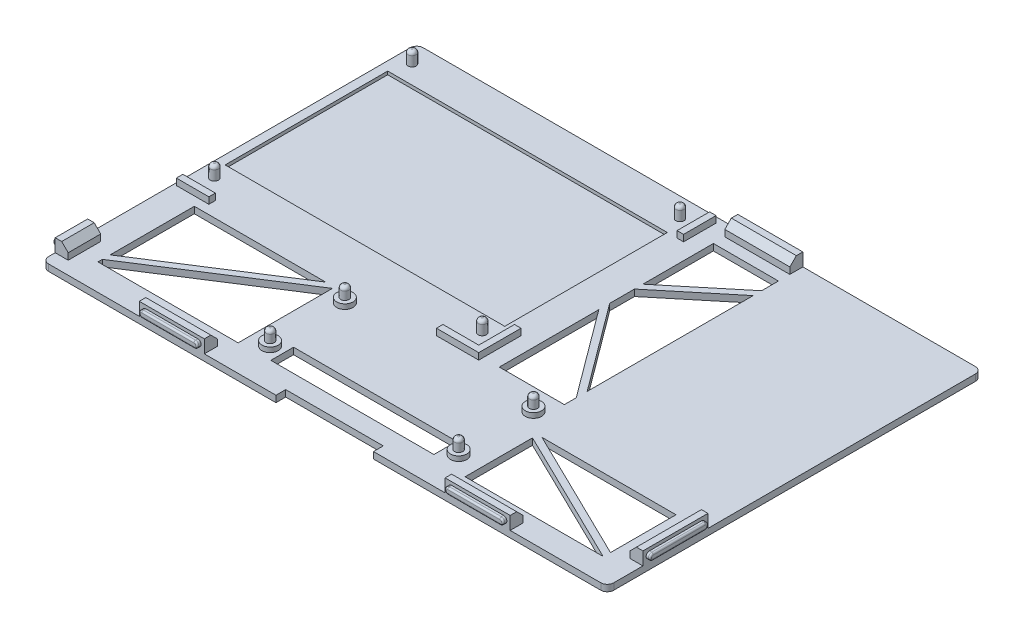
SolidWorks part; units mm, degrees
ref_plane "前基準面" through (0, 0, 0) normal (0, 0, 1) x (1, 0, 0)
ref_plane "上基準面" through (0, 0, 0) normal (0, 1, 0) x (1, 0, 0)
ref_plane "右基準面" through (0, 0, 0) normal (1, 0, 0) x (0, 0, -1)
sketch "草圖1" plane through (0, 0, 0) normal (0, 1, 0) x (1, 0, 0)
  line L0 (0, 57.6) -> (0, -57.6) construction
  line L1 (-86.9, 57.6) -> (86.9, 57.6)
  line L2 (-86.9, 57.6) -> (-86.9, -57.6)
  line L3 (-86.9, -57.6) -> (86.9, -57.6)
  line L4 (86.9, 57.6) -> (86.9, -57.6)
  line L5 (-86.9, 57.6) -> (86.9, -57.6) construction
  line L6 (-86.9, -57.6) -> (86.9, 57.6) construction
  line L7 (-86.9, 0) -> (86.9, 0) construction
  point P0 (0, 0)
  dimension "D1" = 173.8
  dimension "D2" = 115.2
extrude "填料-伸長1" add sketch "草圖1" along normal blind 2
sketch "草圖2" plane through (0, 2, 0) normal (0, 1, 0) x (1, 0, 0)
  line L0 (-86.9, 57.6) -> (-86.9, -57.6) construction
  line L1 (-86.16, 55.93) -> (3.84, 55.93)
  line L2 (-86.16, 55.93) -> (-86.16, -14.07)
  line L3 (-86.16, -14.07) -> (3.84, -14.07)
  line L4 (3.84, 55.93) -> (3.84, -14.07)
  line L5 (-86.16, 55.93) -> (3.84, -14.07) construction
  line L6 (-86.16, -14.07) -> (3.84, 55.93) construction
  line L7 (86.9, 57.6) -> (-86.9, 57.6) construction
  line L8 (-41.16, 55.93) -> (-41.16, -14.07) construction
  line L9 (-86.16, 20.93) -> (3.84, 20.93) construction
  point P0 (-41.16, 20.93)
  dimension "D1" = 90
  dimension "D2" = 70
  dimension "D3" = 0.74
  dimension "D4" = 1.67
sketch "草圖3" plane through (0, 2, 0) normal (0, 1, 0) x (1, 0, 0)
  line L0 (3.84, 55.93) -> (3.84, -14.07) construction
  line L1 (4.84, 55.93) -> (6.84, 55.93)
  line L2 (4.84, 55.93) -> (4.84, 45.93)
  line L3 (4.84, 45.93) -> (6.84, 45.93)
  line L4 (6.84, 55.93) -> (6.84, 45.93)
  line L5 (-86.16, -14.07) -> (3.84, -14.07) construction
  line L7 (4.84, -14.07) -> (4.84, -4.07)
  line L8 (4.84, -4.07) -> (6.84, -4.07)
  line L9 (6.84, -14.07) -> (6.84, -4.07)
  line L10 (6.84, -17.07) -> (-6.16, -17.07)
  line L11 (6.84, -17.07) -> (6.84, -15.07)
  line L12 (4.84, -15.07) -> (-6.16, -15.07)
  line L13 (-6.16, -17.07) -> (-6.16, -15.07)
  line L14 (3.84, -15.07) -> (3.84, -17.07) construction
  line L15 (4.84, -14.07) -> (4.84, -15.07)
  line L16 (6.84, -14.07) -> (6.84, -15.07)
  line L18 (-86.16, -17.07) -> (-76.16, -17.07)
  line L19 (-86.16, -17.07) -> (-86.16, -15.07)
  line L20 (-86.16, -15.07) -> (-76.16, -15.07)
  line L21 (-76.16, -17.07) -> (-76.16, -15.07)
  dimension "D1" = 2
  dimension "D2" = 10
  dimension "D3" = 1
  dimension "D4" = 2
  dimension "D5" = 2
  dimension "D6" = 2
  dimension "D7" = 1
  dimension "D8" = 1
  dimension "D9" = 10
  dimension "D10" = 1
  dimension "D11" = 10
extrude "填料-伸長2" add sketch "草圖3" along normal blind 2
sketch "草圖4" plane through (0, 2, 0) normal (0, 1, 0) x (1, 0, 0)
  line L1 (-86.16, 55.93) -> (3.84, 55.93) construction
  line L2 (3.84, 55.93) -> (3.84, -14.07) construction
  line L3 (-86.16, -14.07) -> (3.84, -14.07) construction
  line L4 (-41.16, 55.93) -> (-41.16, -14.07) construction
  circle A0 centre (0.04, 51.63) radius 1.25
  circle A1 centre (0.04, -9.17) radius 1.25
  circle A2 centre (-82.36, -9.17) radius 1.25
  circle A3 centre (-82.36, 51.63) radius 1.25
  dimension "D1" = 2.5
  dimension "D2" = 3.8
  dimension "D3" = 4.3
  dimension "D4" = 4.9
extrude "填料-伸長3" add sketch "草圖4" along normal blind 4
fillet "圓角2" radius 1 4 edges at (-82.36, 6, -52.88) (-82.36, 6, 7.92) (0.04, 6, 10.42) (0.04, 6, -50.38)
sketch "草圖5" plane through (0, 2, 0) normal (0, 1, 0) x (1, 0, 0)
  line L0 (-86.16, 55.93) -> (3.84, -14.07) construction
  line L1 (-84.16, 45.93) -> (1.84, 45.93)
  line L2 (-84.16, 45.93) -> (-84.16, -4.07)
  line L3 (-84.16, -4.07) -> (1.84, -4.07)
  line L4 (1.84, 45.93) -> (1.84, -4.07)
  line L5 (-84.16, 45.93) -> (1.84, -4.07) construction
  line L6 (-84.16, -4.07) -> (1.84, 45.93) construction
  line L7 (-86.16, 55.93) -> (3.84, 55.93) construction
  line L8 (-86.16, 55.93) -> (-86.16, -14.07) construction
  point P0 (-41.16, 20.93)
  dimension "D1" = 10
  dimension "D2" = 2
extrude "除料-伸長1" cut sketch "草圖5" against normal blind 1
sketch "草圖6" plane through (0, 2, 0) normal (0, 1, 0) x (1, 0, 0)
  line L1 (35.1797, 56.0179) -> (85.1797, 56.0179)
  line L2 (35.1797, 56.0179) -> (35.1797, -24.9821)
  line L3 (35.1797, -24.9821) -> (85.1797, -24.9821)
  line L4 (85.1797, 56.0179) -> (85.1797, -24.9821)
  line L5 (35.1797, 56.0179) -> (85.1797, -24.9821) construction
  line L6 (35.1797, -24.9821) -> (85.1797, 56.0179) construction
  point P0 (60.1797, 15.5179)
  dimension "D1" = 81
  dimension "D2" = 50
sketch "草圖7" plane through (0, 2, 0) normal (0, 1, 0) x (1, 0, 0)
  line L0 (0, 57.6) -> (0, -57.6) construction
  line L1 (-32.5, -18.9) -> (32.5, -18.9)
  line L2 (-32.5, -18.9) -> (-32.5, -49.1)
  line L3 (-32.5, -49.1) -> (32.5, -49.1)
  line L4 (32.5, -18.9) -> (32.5, -49.1)
  line L5 (-32.5, -18.9) -> (32.5, -49.1) construction
  line L6 (-32.5, -49.1) -> (32.5, -18.9) construction
  line L7 (-86.9, -57.6) -> (86.9, -57.6) construction
  point P0 (0, -34)
  point P5 (32.5, -34)
  dimension "D1" = 65
  dimension "D2" = 30.2
  dimension "D3" = 8.5
sketch "草圖8" plane through (0, 2, 0) normal (0, 1, 0) x (1, 0, 0)
  line L0 (-32.5, -18.9) -> (32.5, -18.9) construction
  line L1 (32.5, -18.9) -> (32.5, -49.1) construction
  line L2 (-32.5, -49.1) -> (32.5, -49.1) construction
  line L3 (0, -18.9) -> (0, -49.1) construction
  circle A0 centre (29, -22.4) radius 2.5
  circle A1 centre (29, -22.4) radius 1.25
  circle A2 centre (29, -45.4) radius 2.5
  circle A3 centre (29, -45.4) radius 1.25
  circle A4 centre (-29, -45.4) radius 1.25
  circle A5 centre (-29, -45.4) radius 2.5
  circle A6 centre (-29, -22.4) radius 1.25
  circle A7 centre (-29, -22.4) radius 2.5
  dimension "D1" = 5
  dimension "D4" = 2.5
  dimension "D2" = 3.5
  dimension "D3" = 3.5
  dimension "D5" = 3.7
extrude "填料-伸長4" add sketch "草圖8" along normal blind 1.5 contours A6 | A7 A6 | A5 A4 | A4 | A0 A1 | A1 | A2 A3 | A3 region at (26.5707, 2, 22.4) region at (29, 2, 22.4) region at (26.5707, 2, 45.4) region at (29, 2, 45.4) region at (-29, 2, 45.4) region at (-31.4293, 2, 45.4) region at (-29, 2, 22.4) region at (-31.4293, 2, 22.4)
extrude "填料-伸長5" add sketch "草圖8<3>" along normal blind 5 contours A6 | A4 | A3 | A1 region at (29, 2, 22.4) region at (29, 2, 45.4) region at (-29, 2, 45.4) region at (-29, 2, 22.4)
sketch "草圖8<3>" plane through (0, 2, 0) normal (0, 1, 0) x (1, 0, 0) same geometry as "草圖8"
fillet "圓角3" radius 1 4 edges at (-29, 7, 46.65) (29, 7, 46.65) (29, 7, 23.65) (-29, 7, 23.65)
sketch "草圖9" plane through (0, 2, 0) normal (0, 1, 0) x (1, 0, 0)
  line L0 (0, 57.6) -> (0, -57.6) construction
  line L1 (-25.0798, -42.1) -> (25.0798, -42.1)
  line L2 (-25.0798, -42.1) -> (-25.0798, -49.1)
  line L3 (-25.0798, -49.1) -> (25.0798, -49.1)
  line L4 (25.0798, -42.1) -> (25.0798, -49.1)
  line L5 (-25.0798, -42.1) -> (25.0798, -49.1) construction
  line L6 (-25.0798, -49.1) -> (25.0798, -42.1) construction
  line L7 (-32.5, -49.1) -> (32.5, -49.1) construction
  line L8 (-86.9, -57.6) -> (86.9, -57.6) construction
  line L9 (-15, -54.6) -> (15, -54.6)
  line L10 (-15, -54.6) -> (-15, -57.6)
  line L11 (-15, -57.6) -> (15, -57.6)
  line L12 (15, -54.6) -> (15, -57.6)
  line L13 (-15, -54.6) -> (15, -57.6) construction
  line L14 (-15, -57.6) -> (15, -54.6) construction
  point P0 (0, -45.6)
  point P9 (0, -56.1)
  dimension "D1" = 7
  dimension "D2" = 3
  dimension "D3" = 30
extrude "除料-伸長2" cut sketch "草圖9" against normal blind 2
sketch "草圖10" plane through (0, 2, 0) normal (0, 1, 0) x (1, 0, 0)
  line L0 (-86.9, 57.6) -> (86.9, 57.6) construction
  line L1 (11.8547, 57.6) -> (31.8547, 57.6)
  line L2 (11.8547, 57.6) -> (11.8547, 53.6)
  line L3 (11.8547, 53.6) -> (31.8547, 53.6)
  line L4 (31.8547, 57.6) -> (31.8547, 53.6)
  line L5 (0, 57.6) -> (0, -57.6) construction
  line L10 (86.9, 57.6) -> (86.9, -57.6) construction
  line L11 (86.9, -26.638) -> (82.9, -26.638)
  line L12 (86.9, -26.638) -> (86.9, -46.638)
  line L13 (86.9, -46.638) -> (82.9, -46.638)
  line L14 (82.9, -26.638) -> (82.9, -46.638)
  line L15 (-86.9, -57.6) -> (86.9, -57.6) construction
  line L16 (37.0319, -57.6) -> (57.0319, -57.6)
  line L17 (37.0319, -57.6) -> (37.0319, -53.6)
  line L18 (37.0319, -53.6) -> (57.0319, -53.6)
  line L19 (57.0319, -57.6) -> (57.0319, -53.6)
  line L20 (-57.0319, -57.6) -> (-57.0319, -53.6)
  line L21 (-37.0319, -53.6) -> (-57.0319, -53.6)
  line L22 (-37.0319, -57.6) -> (-37.0319, -53.6)
  line L23 (-37.0319, -57.6) -> (-57.0319, -57.6)
  line L24 (-86.9, 57.6) -> (-86.9, -57.6) construction
  line L25 (-86.9, -53.6) -> (-82.9, -53.6)
  line L26 (-86.9, -53.6) -> (-86.9, -43.6)
  line L27 (-86.9, -43.6) -> (-82.9, -43.6)
  line L28 (-82.9, -53.6) -> (-82.9, -43.6)
  dimension "D1" = 4
  dimension "D2" = 20
  dimension "D3" = 4
  dimension "D4" = 10
  dimension "D5" = 20
  dimension "D6" = 4
  dimension "D7" = 20
  dimension "D8" = 4
extrude "填料-伸長6" add sketch "草圖10" along normal blind 4
sketch "草圖11" plane through (0, 2, 0) normal (0, 1, 0) x (1, 0, 0)
  line L0 (-77.8796, -45.7226) -> (-37.4971, -19.8239)
  line L1 (-77.8796, -49.4672) -> (-34.7645, -49.4672)
  line L2 (-77.8796, -49.4672) -> (-77.8796, -48.0986)
  line L3 (-77.8796, -19.8239) -> (-37.4971, -19.8239)
  line L4 (-34.7645, -49.4672) -> (-34.7645, -20.4474)
  line L5 (-77.8796, -48.0986) -> (-34.7645, -20.4474)
  line L6 (-77.8796, -45.7226) -> (-77.8796, -19.8239)
  line L7 (31.8547, 44.9175) -> (11.8547, 28.4103)
  line L8 (11.8547, 50.0907) -> (31.8547, 50.0907)
  line L9 (11.8547, 50.0907) -> (11.8547, 28.4103)
  line L10 (11.8547, -15.7529) -> (31.8547, -15.7529)
  line L11 (31.8547, 50.0907) -> (31.8547, 44.9175)
  line L13 (11.8547, 25.8171) -> (31.8547, 42.3243)
  line L14 (11.8547, 18.1985) -> (31.8547, -8.7367)
  line L15 (11.8547, 14.8436) -> (31.8547, -12.0916)
  line L16 (31.8547, 42.3243) -> (31.8547, -8.7367)
  line L17 (11.8547, 25.8171) -> (11.8547, 18.1985)
  line L18 (11.8547, 14.8436) -> (11.8547, -15.7529)
  line L19 (31.8547, -12.0916) -> (31.8547, -15.7529)
  line L20 (78.3594, -48.0628) -> (37.1158, -27.9151)
  line L21 (37.1158, -27.9151) -> (78.3594, -27.9151)
  line L22 (35.8042, -29.5002) -> (35.8042, -50.2291)
  line L23 (35.8042, -50.2291) -> (78.2374, -50.2291)
  line L24 (78.3594, -27.9151) -> (78.3594, -48.0628)
  line L25 (35.8042, -29.5002) -> (78.2374, -50.2291)
  dimension "D1" = 2
  dimension "D2" = 2
  dimension "D3" = 2
  dimension "D4" = 2
extrude "除料-伸長3" cut sketch "草圖11" against normal through all
fillet "圓角1" radius 2 4 edges at (86.9, 1, -57.6) (-86.9, 1, -57.6) (-86.9, 1, 57.6) (86.9, 1, 57.6)
chamfer "導角1" distance 2 angle 45 5 edges at (82.9, 6, 36.638) (47.0319, 6, 53.6) (-47.0319, 6, 53.6) (-82.9, 6, 48.6) (21.8547, 6, -53.6)
sketch "草圖13" plane through (86.9, 0, 0) normal (1, 0, 0) x (0, 0, -1)
  line L0 (-44.638, 4) -> (-28.638, 4) construction
  line L1 (-44.638, 5) -> (-28.638, 5)
  line L2 (-44.638, 3) -> (-28.638, 3)
  line L4 (-46.638, 4) -> (-26.638, 4) construction
  line L5 (-46.638, 6) -> (-46.638, 2) construction
  arc A0 (-44.638, 5) -> (-44.638, 3) centre (-44.638, 4) ccw
  arc A1 (-28.638, 3) -> (-28.638, 5) centre (-28.638, 4) ccw
  point P2 (-36.638, 4)
  point P16 (-36.638, 4)
  dimension "D1" = 2
  dimension "D2" = 16
extrude "填料-伸長8" add sketch "草圖13" along normal blind 1.2
sketch "草圖14" plane through (0, 0, -57.6) normal (0, 0, -1) x (-1, 0, 0)
  line L0 (-31.8547, 4) -> (-11.8547, 4) construction
  line L1 (-31.8547, 6) -> (-31.8547, 2) construction
  line L2 (-29.8547, 4) -> (-13.8547, 4) construction
  line L3 (-29.8547, 5) -> (-13.8547, 5)
  line L4 (-29.8547, 3) -> (-13.8547, 3)
  arc A0 (-29.8547, 5) -> (-29.8547, 3) centre (-29.8547, 4) ccw
  arc A1 (-13.8547, 3) -> (-13.8547, 5) centre (-13.8547, 4) ccw
  point P7 (-21.8547, 4)
  point P13 (-21.8547, 4)
  dimension "D1" = 16
  dimension "D2" = 2
extrude "填料-伸長9" add sketch "草圖14" along normal blind 1.2
sketch "草圖15" plane through (0, 0, 57.6) normal (0, 0, 1) x (1, 0, 0)
  line L0 (-57.0319, 4) -> (-37.0319, 4) construction
  line L1 (-57.0319, 6) -> (-57.0319, 2) construction
  line L2 (-37.0319, 6) -> (-37.0319, 2) construction
  line L3 (-55.0319, 4) -> (-39.0319, 4) construction
  line L4 (-55.0319, 5) -> (-39.0319, 5)
  line L5 (-55.0319, 3) -> (-39.0319, 3)
  line L6 (0, 2) -> (0, 0) construction
  line L7 (55.0319, 4) -> (39.0319, 4) construction
  line L8 (55.0319, 5) -> (39.0319, 5)
  line L9 (55.0319, 3) -> (39.0319, 3)
  arc A0 (-55.0319, 5) -> (-55.0319, 3) centre (-55.0319, 4) ccw
  arc A1 (-39.0319, 3) -> (-39.0319, 5) centre (-39.0319, 4) ccw
  arc A2 (55.0319, 5) -> (55.0319, 3) centre (55.0319, 4) cw
  arc A3 (39.0319, 3) -> (39.0319, 5) centre (39.0319, 4) cw
  point P8 (-47.0319, 4)
  point P16 (47.0319, 4)
  dimension "D1" = 16
  dimension "D2" = 2
extrude "填料-伸長11" add sketch "草圖15" along normal blind 1.2
sketch "草圖16" plane through (-86.9, 0, 0) normal (-1, 0, 0) x (0, 0, 1)
  line L0 (43.6, 4) -> (53.6, 4) construction
  line L1 (43.6, 6) -> (43.6, 2) construction
  line L2 (53.6, 6) -> (53.6, 2) construction
  line L3 (45.1, 4) -> (52.1, 4) construction
  line L4 (45.1, 5) -> (52.1, 5)
  line L5 (45.1, 3) -> (52.1, 3)
  arc A0 (45.1, 5) -> (45.1, 3) centre (45.1, 4) ccw
  arc A1 (52.1, 3) -> (52.1, 5) centre (52.1, 4) ccw
  point P8 (48.6, 4)
  dimension "D1" = 7
  dimension "D2" = 2
extrude "填料-伸長12" add sketch "草圖16" along normal blind 1.2
fillet "圓角4" radius 0.5 20 edges at (12.8547, 4, -58.8) (21.8547, 3, -58.8) (30.8547, 4, -58.8) (88.1, 4, 27.638) (88.1, 3, 36.638) (88.1, 4, 45.638) (56.0319, 4, 58.8) (47.0319, 3, 58.8) (38.0319, 4, 58.8) (-88.1, 4, 53.1) (-88.1, 3, 48.6) (-88.1, 4, 44.1) (-38.0319, 4, 58.8) (-47.0319, 3, 58.8) (-56.0319, 4, 58.8) (21.8547, 5, -58.8) (88.1, 5, 36.638) (47.0319, 5, 58.8) (-88.1, 5, 48.6) (-47.0319, 5, 58.8)
